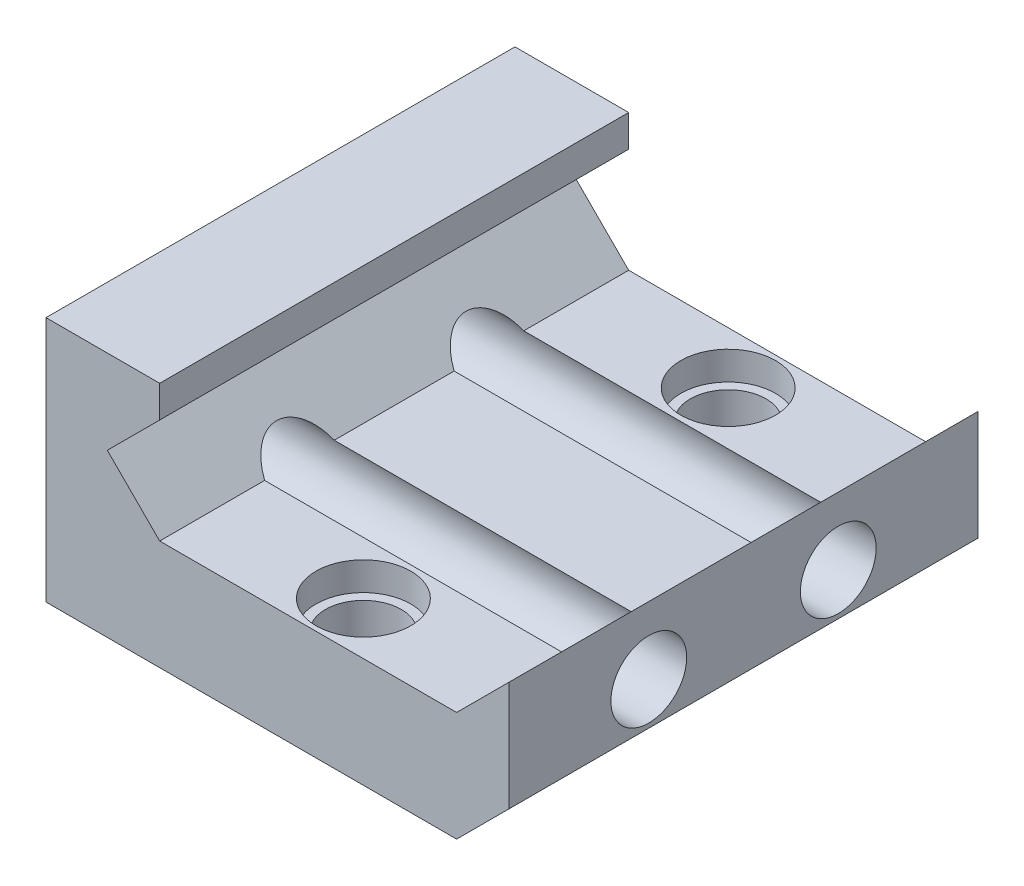
SolidWorks part; units mm, degrees
ref_plane "Płaszczyzna przednia" through (0, 0, 0) normal (0, 0, 1) x (1, 0, 0)
ref_plane "Płaszczyzna górna" through (0, 0, 0) normal (0, 1, 0) x (1, 0, 0)
ref_plane "Płaszczyzna prawa" through (0, 0, 0) normal (1, 0, 0) x (0, 0, -1)
sketch "Szkic1" plane through (0, 0, 0) normal (0, 0, 1) x (1, 0, 0)
  line L0 (-14, 5.4617) -> (-8, 5.4617)
  line L2 (-14, -7.5383) -> (-14, 5.4617)
  line L5 (-14, -7.5383) -> (13.9258, 7.4984) construction
  line L6 (-14, 5.4617) -> (14.0994, -5.5005) construction
  line L7 (-8, 5.4617) -> (-8, 3.7817)
  line L8 (-8, 3.7817) -> (-10.765, 1.0167)
  line L9 (-10.765, 1.0167) -> (-8, -1.7483)
  line L10 (-8, -1.7483) -> (7.67, -1.7483)
  line L11 (7.67, -1.7483) -> (10.435, 1.0167)
  line L14 (10.435, 1.0167) -> (10.435, -4.7733)
  line L17 (10.435, -4.7733) -> (7.67, -7.5383)
  line L18 (-14, -7.5383) -> (7.67, -7.5383)
  point P0 (0, 0)
  point P6 (0, 0)
  point P14 (0, 0)
  dimension "D1" = 28
  dimension "D2" = 13
  dimension "D3" = 6
  dimension "D4" = 1.68
  dimension "D5" = 13
  dimension "D6" = 5.79
extrude "Dodanie-wyciągnięcie3" add sketch "Szkic1" along normal blind 24.75
sketch "Szkic3" plane through (10.435, 0, 0) normal (1, 0, 0) x (0, 0, -1)
  line L0 (-24.75, -7.5383) -> (0, -7.5383) construction
  line L2 (0, -4.7733) -> (0, 1.0167) construction
  circle A0 centre (-17.375, -2.5383) radius 2
  circle A1 centre (-7.375, -2.5383) radius 2
  dimension "D1" = 10
  dimension "D2" = 7.375
  dimension "D3" = 5
  dimension "D4" = 5
extrude "Wytnij-wyciągnięcie1" cut sketch "Szkic3" against normal blind 24.75
sketch "Szkic4" plane through (0, -1.7483, 0) normal (0, 1, 0) x (1, 0, 0)
  line L0 (7.67, -24.75) -> (-8, -24.75) construction
  circle A0 centre (0, -2.75) radius 2
  circle A1 centre (0, -22) radius 2
  dimension "D2" = 2.75
  dimension "D3" = 2.75
extrude "Wytnij-wyciągnięcie2" cut sketch "Szkic4" against normal blind 6
sketch "Szkic7" plane through (0, -1.7483, 0) normal (0, 1, 0) x (1, 0, 0)
  circle A0 centre (0, -2.75) radius 2.5
  circle A1 centre (0, -22) radius 2.5
  dimension "D1" = 2.75
  dimension "D2" = 19.25
extrude "Wytnij-wyciągnięcie3" cut sketch "Szkic7" against normal blind 1.5
sketch "Szkic8" plane through (0, -1.7483, 0) normal (0, 1, 0) x (1, 0, 0)
  line L1 (10.435, -24.75) -> (10.435, 0) construction
  line L2 (-10.765, -15) -> (10.435, -15)
  line L3 (-10.765, -15) -> (-10.765, -9.75)
  line L4 (-10.765, -9.75) -> (10.435, -9.75)
  line L5 (10.435, -15) -> (10.435, -9.75)
  line L6 (-10.765, -15) -> (10.435, -9.75) construction
  line L7 (-10.765, -9.75) -> (10.435, -15) construction
  line L9 (10.435, -24.75) -> (10.435, 0) construction
  line L10 (-10.765, -4.75) -> (10.435, -4.75)
  line L11 (-10.765, -4.75) -> (-10.765, 0)
  line L12 (-10.765, 0) -> (10.435, 0)
  line L13 (10.435, -4.75) -> (10.435, 0)
  line L14 (-10.765, -4.75) -> (10.435, 0) construction
  line L15 (-10.765, 0) -> (10.435, -4.75) construction
  line L16 (-10.765, -20) -> (10.435, -20)
  line L17 (-10.765, -20) -> (-10.765, -24.75)
  line L18 (-10.765, -24.75) -> (10.435, -24.75)
  line L19 (10.435, -20) -> (10.435, -24.75)
  line L20 (-10.765, -20) -> (10.435, -24.75) construction
  line L21 (-10.765, -24.75) -> (10.435, -20) construction
  dimension "D1" = 5.25
  dimension "D2" = 21.2
